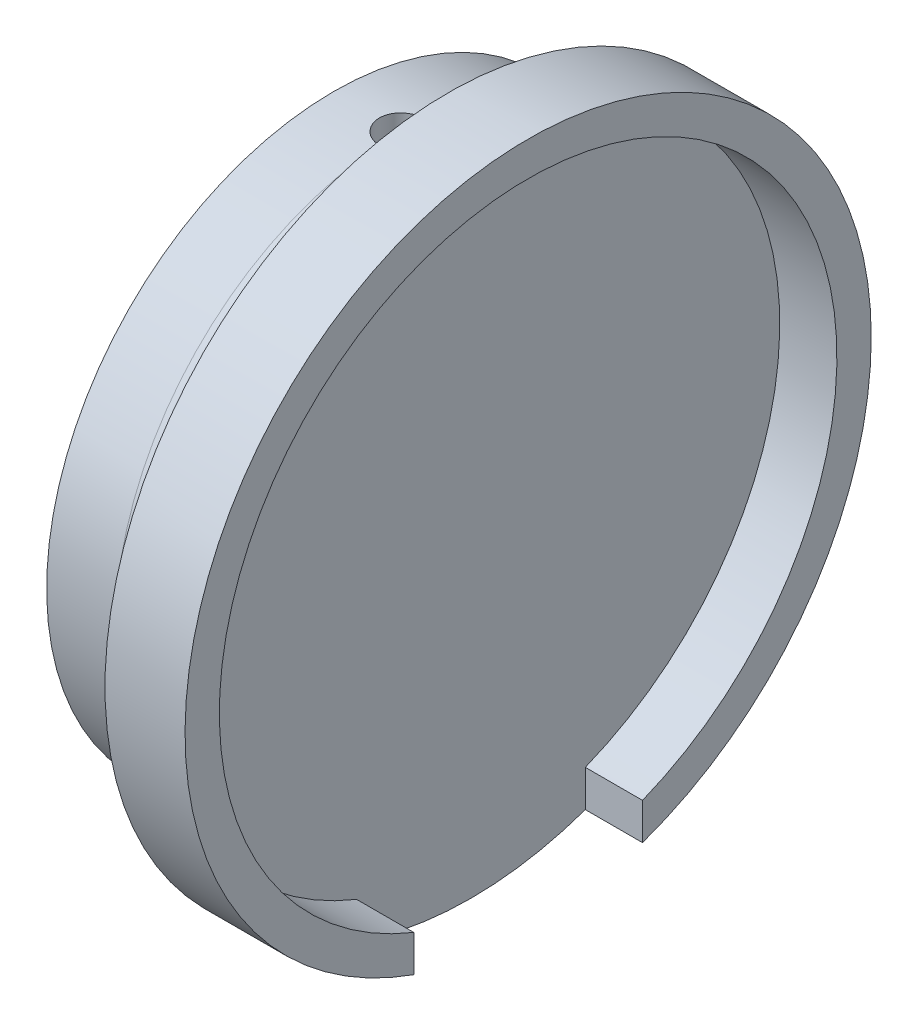
SolidWorks part; units mm, degrees
ref_plane "前视基准面" through (0, 0, 0) normal (0, 0, 1) x (1, 0, 0)
ref_plane "上视基准面" through (0, 0, 0) normal (0, 1, 0) x (1, 0, 0)
ref_plane "右视基准面" through (0, 0, 0) normal (1, 0, 0) x (0, 0, -1)
other "Configuration Table"
sketch "草图1" plane through (0, 0, 0) normal (1, 0, 0) x (0, 0, -1)
  circle A0 centre (0, 0) radius 12.55
  dimension "D1" = 25.1
extrude "凸台-拉伸1" add sketch "草图1" along normal blind 6
sketch "草图2" plane through (0, 0, 0) normal (-1, 0, 0) x (0, 0, 1)
  circle A0 centre (0, 0) radius 3.2
  dimension "D1" = 6.4
extrude "切除-拉伸1" cut sketch "草图2" against normal blind 6
sketch "草图3" plane through (0, 0, 0) normal (0, 1, 0) x (1, 0, 0)
  line L0 (0, 12.55) -> (0, -12.55) construction
  circle A0 centre (3, 0) radius 1
  dimension "D1" = 2
  dimension "D2" = 3
extrude "切除-拉伸2" cut sketch "草图3" against normal up to next and the other way up to next
sketch "草图4" plane through (6, 0, 0) normal (1, 0, 0) x (0, 0, -1)
  circle A0 centre (0, 0) radius 15
  dimension "D1" = 30
extrude "凸台-拉伸2" add sketch "草图4" along normal blind 2.5 and the other way blind 1
sketch "草图5" plane through (8.5, 0, 0) normal (1, 0, 0) x (0, 0, -1)
  circle A0 centre (0, 0) radius 13.5
  dimension "D1" = 27
extrude "切除-拉伸3" cut sketch "草图5" against normal blind 2.5
fillet "圆角2" radius 2 1 edges at (5, 0, -12.55)
sketch "草图7" plane through (0, 0, 0) normal (0, 1, 0) x (1, 0, 0)
  line L0 (0, 0) -> (8.5, 0) construction
  line L1 (8.5, -15) -> (8.5, 15) construction
  line L3 (8.5, 5) -> (6, 5)
  line L4 (8.5, 5) -> (8.5, -5)
  line L5 (8.5, -5) -> (6, -5)
  line L6 (6, 5) -> (6, -5)
  dimension "D1" = 2.5
  dimension "D2" = 10
  dimension "D3" = 5
extrude "切除-拉伸4" cut sketch "草图7" against normal blind 21
